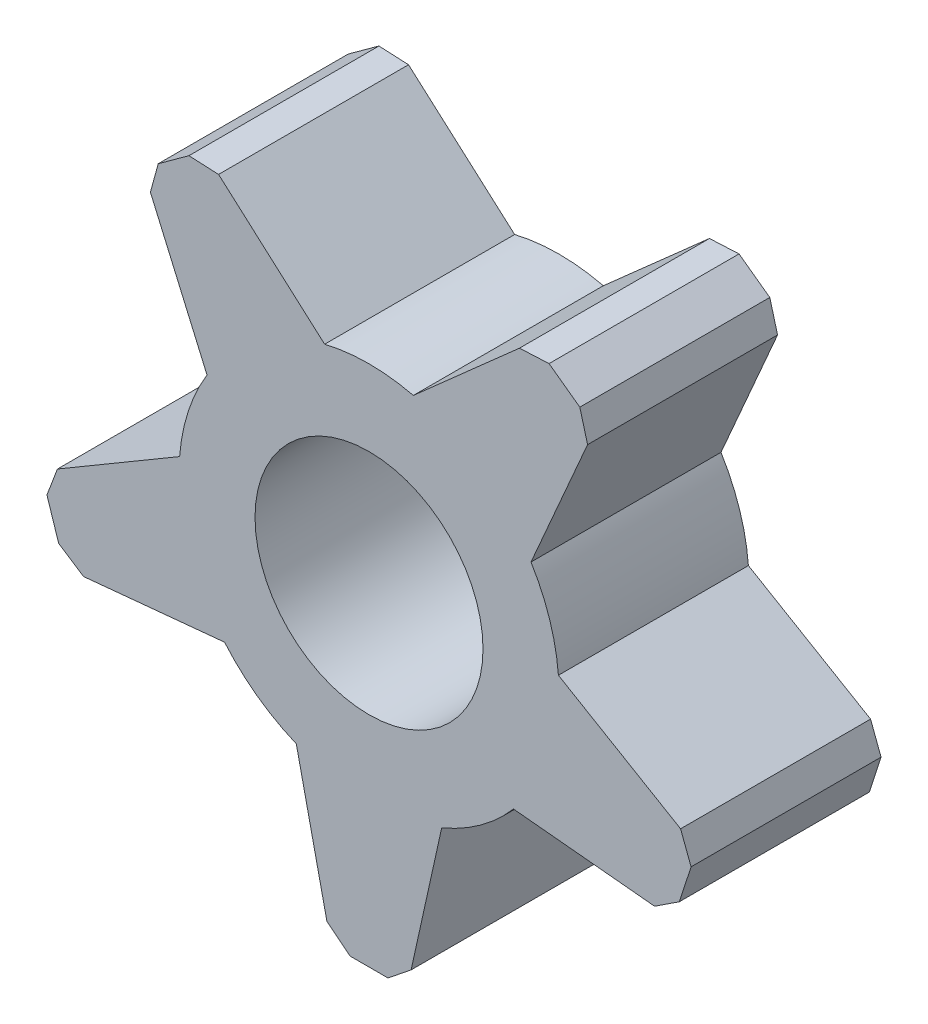
SolidWorks part; units mm, degrees
ref_plane "Front Plane" through (0, 0, 0) normal (0, 0, 1) x (1, 0, 0)
ref_plane "Top Plane" through (0, 0, 0) normal (0, 1, 0) x (1, 0, 0)
ref_plane "Right Plane" through (0, 0, 0) normal (1, 0, 0) x (0, 0, -1)
sketch "Sketch1" plane through (0, 0, 0) normal (0, 0, 1) x (1, 0, 0)
  line L0 (0, 0) -> (0, -10) construction
  line L1 (0, -10) -> (0, -17.5) construction
  line L2 (1, -17.5) -> (-1, -17.5)
  line L3 (-3.8268, -9.2388) -> (-2.2159, -16.5236)
  line L4 (3.8268, -9.2388) -> (2.2159, -16.5236)
  line L5 (-2.2159, -16.5236) -> (-1, -17.5)
  line L6 (2.2159, -16.5236) -> (1, -17.5)
  line L7 (-16.3345, -6.3589) -> (-16.9525, -4.4567)
  line L8 (-9.9692, 0.7846) -> (-16.3996, -2.9986)
  line L9 (-7.6041, -6.4945) -> (-15.0301, -7.2135)
  line L10 (-16.3996, -2.9986) -> (-16.9525, -4.4567)
  line L11 (-15.0301, -7.2135) -> (-16.3345, -6.3589)
  line L12 (-9.5106, -3.0902) -> (-16.6435, -5.4078) construction
  line L13 (-11.0953, 13.57) -> (-9.4772, 14.7456)
  line L14 (-2.3345, 9.7237) -> (-7.9196, 14.6703)
  line L15 (-8.5264, 5.225) -> (-11.505, 12.0654)
  line L16 (-7.9196, 14.6703) -> (-9.4772, 14.7456)
  line L17 (-11.505, 12.0654) -> (-11.0953, 13.57)
  line L18 (-5.8779, 8.0902) -> (-10.2862, 14.1578) construction
  line L19 (9.4772, 14.7456) -> (11.0953, 13.57)
  line L20 (8.5264, 5.225) -> (11.505, 12.0654)
  line L21 (2.3345, 9.7237) -> (7.9196, 14.6703)
  line L22 (11.505, 12.0654) -> (11.0953, 13.57)
  line L23 (7.9196, 14.6703) -> (9.4772, 14.7456)
  line L24 (5.8779, 8.0902) -> (10.2862, 14.1578) construction
  line L25 (16.9525, -4.4567) -> (16.3345, -6.3589)
  line L26 (7.6041, -6.4945) -> (15.0301, -7.2135)
  line L27 (9.9692, 0.7846) -> (16.3996, -2.9986)
  line L28 (15.0301, -7.2135) -> (16.3345, -6.3589)
  line L29 (16.3996, -2.9986) -> (16.9525, -4.4567)
  line L30 (9.5106, -3.0902) -> (16.6435, -5.4078) construction
  circle A0 centre (0, 0) radius 10
  arc A1 (0, -10) -> (-3.8268, -9.2388) centre (0, 0) cw
  arc A2 (0, -10) -> (3.8268, -9.2388) centre (0, 0) ccw
  arc A3 (-9.5106, -3.0902) -> (-9.9692, 0.7846) centre (0, 0) cw
  arc A4 (-9.5106, -3.0902) -> (-7.6041, -6.4945) centre (0, 0) ccw
  arc A5 (-5.8779, 8.0902) -> (-2.3345, 9.7237) centre (0, 0) cw
  arc A6 (-5.8779, 8.0902) -> (-8.5264, 5.225) centre (0, 0) ccw
  arc A7 (5.8779, 8.0902) -> (8.5264, 5.225) centre (0, 0) cw
  arc A8 (5.8779, 8.0902) -> (2.3345, 9.7237) centre (0, 0) ccw
  arc A9 (9.5106, -3.0902) -> (7.6041, -6.4945) centre (0, 0) cw
  arc A10 (9.5106, -3.0902) -> (9.9692, 0.7846) centre (0, 0) ccw
  circle A11 centre (0, 0) radius 6
  point P8 (-2, -17.5)
  point P9 (2, -17.5)
  point P10 (0, -17.5)
  point P21 (-17.2615, -3.5057)
  point P22 (-16.0255, -7.3099)
  point P23 (-16.6435, -5.4078)
  point P32 (-8.6682, 15.3334)
  point P33 (-11.9043, 12.9822)
  point P34 (-10.2862, 14.1578)
  point P43 (11.9043, 12.9822)
  point P44 (8.6682, 15.3334)
  point P45 (10.2862, 14.1578)
  point P54 (16.0255, -7.3099)
  point P55 (17.2615, -3.5057)
  point P56 (16.6435, -5.4078)
  dimension "D1" = 5
extrude "Boss-Extrude1" add sketch "Sketch1" along normal blind 5 and the other way blind 5 contours A0 A11 | A0 L3 L5 L2 L6 L4 | A0 L8 L10 L7 L11 L9 | A0 L14 L16 L13 L17 L15 | A0 L20 L22 L19 L23 L21 | A0 L26 L28 L25 L29 L27 region at (0, -13.1492, 0) region at (1.8957, -9.5304, 0) region at (12.5057, -4.0633, 0) region at (-12.5057, -4.0633, 0) region at (-7.7289, 10.638, 0) region at (7.7289, 10.638, 0)
